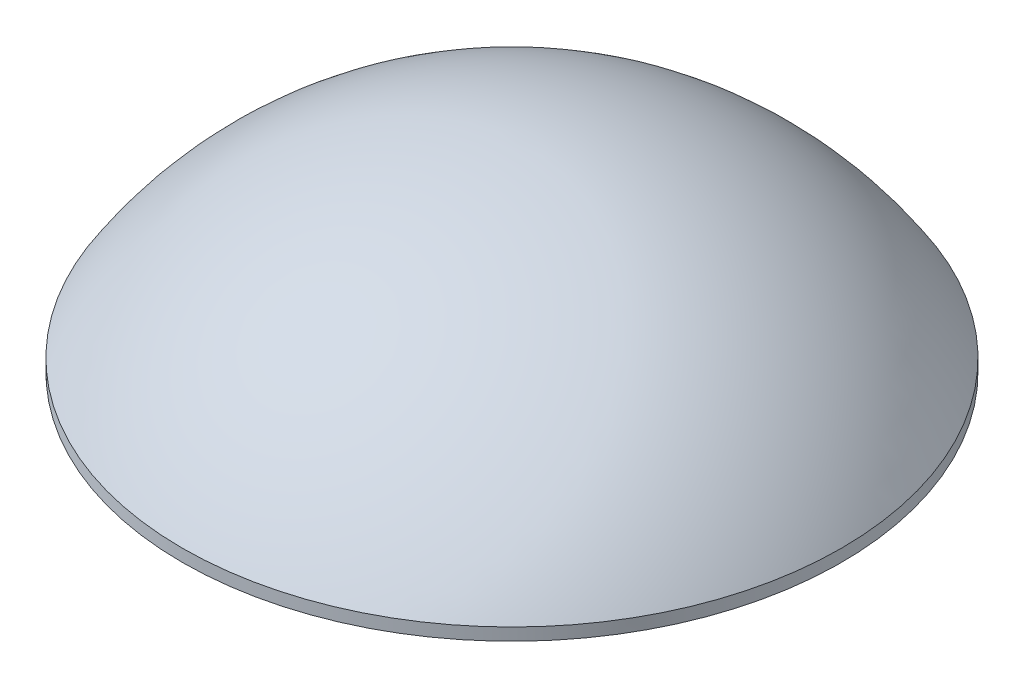
SolidWorks part; units mm, degrees
ref_plane "Front Plane" through (0, 0, 0) normal (0, 0, 1) x (1, 0, 0)
ref_plane "Top Plane" through (0, 0, 0) normal (0, 1, 0) x (1, 0, 0)
ref_plane "Right Plane" through (0, 0, 0) normal (1, 0, 0) x (0, 0, -1)
ref_axis "mirrorX" through (-165, 0, 0) along (1, 0, 0)
sketch "Sketch2" plane through (0, 0, 0) normal (0, 0, 1) x (1, 0, 0)
  line L0 (-102.6109, 79.8185) -> (-102.6109, 75.056)
  line L1 (0, 130) -> (0, 150)
  line L4 (-127, 79.8185) -> (-127, 75.056)
  line L5 (-127, 75.056) -> (-102.6109, 75.056)
  arc A0 (0, 150) -> (-127, 79.8185) centre (0, 0) ccw
  arc A1 (0, 130) -> (-102.6109, 79.8185) centre (0, 0) ccw
  dimension "D2" = 4.7625
ref_axis "mirrorZ" through (0, 153.7472, 0) along (0, -1, 0)
revolve "Revolve4" add sketch "Sketch2" angle 360 about axis through (0, 153.7472, 0) along (0, -1, 0)
ref_plane "MirrorCenterPlane" through (0, 0, 0) normal (0, -1, 0) x (-1, 0, 0)
ref_plane "MirrorFocusPlane" through (0, 50, 0) normal (0, -1, 0) x (-1, 0, 0)
